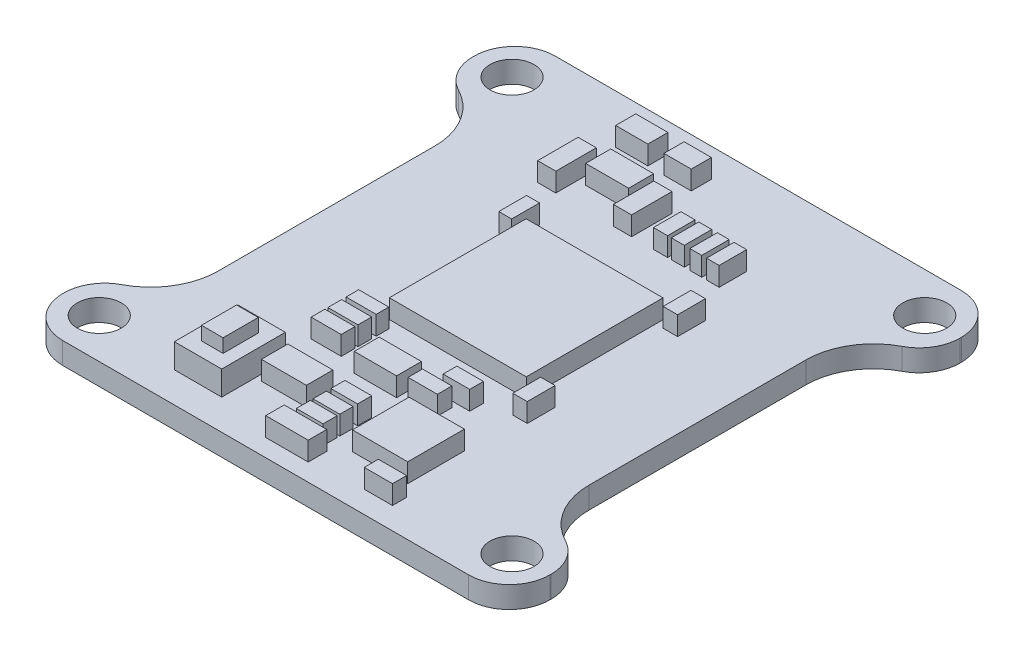
SolidWorks part; units mm, degrees
ref_plane "Front Plane" through (0, 0, 0) normal (0, 0, 1) x (1, 0, 0)
ref_plane "Top Plane" through (0, 0, 0) normal (0, 1, 0) x (1, 0, 0)
ref_plane "Right Plane" through (0, 0, 0) normal (1, 0, 0) x (0, 0, -1)
sketch "Sketch1" plane through (0, 0, 0) normal (0, 1, 0) x (1, 0, 0)
  line L0 (0, 18.2) -> (0, -18.2) construction
  line L1 (-18, 18.2) -> (18, 18.2)
  line L2 (-18, 18.2) -> (-18, -18.2)
  line L3 (-18, -18.2) -> (18, -18.2)
  line L4 (18, 18.2) -> (18, -18.2)
  line L5 (-18, 18.2) -> (18, -18.2) construction
  line L6 (-18, -18.2) -> (18, 18.2) construction
  line L7 (13.7, 18.2) -> (-13.7, 18.2)
  line L8 (13.7, 18.2) -> (13.7, -18.2)
  line L9 (13.7, -18.2) -> (-13.7, -18.2)
  line L10 (-13.7, 18.2) -> (-13.7, -18.2)
  line L11 (13.7, 18.2) -> (-13.7, -18.2) construction
  line L12 (13.7, -18.2) -> (-13.7, 18.2) construction
  line L13 (-18, 0) -> (18, 0) construction
  line L15 (18, 12.1) -> (-18, 12.1)
  line L16 (18, 12.1) -> (18, -12.1)
  line L17 (18, -12.1) -> (-18, -12.1)
  line L18 (-18, 12.1) -> (-18, -12.1)
  line L19 (18, 12.1) -> (-18, -12.1) construction
  line L20 (18, -12.1) -> (-18, 12.1) construction
  circle A0 centre (-15.25, 15.25) radius 1.625
  circle A1 centre (15.25, 15.25) radius 1.625
  circle A2 centre (15.25, -15.25) radius 1.625
  circle A3 centre (-15.25, -15.25) radius 1.625
  point P0 (0, 0)
  point P5 (0, 0)
  point P23 (0, 0)
  dimension "D4" = 3.25
  dimension "D1" = 36.4
  dimension "D2" = 36
  dimension "D3" = 27.4
  dimension "D5" = 30.5
  dimension "D6" = 30.5
  dimension "D7" = 24.2
extrude "PCB" add sketch "Sketch1" along normal blind 1.6 contours L15 L8 L1 L10 | L17 L8 L15 L10 | L4 L17 L8 L3 A2 | L8 L17 L10 L3 | L10 L17 L2 L3 A3 | L15 L4 L1 L8 A1 | L15 L10 L1 L2 A0 region at (-15.85, 0, -18.1254) region at (0, 0, -15.1499) region at (15.85, 0, -18.1254) region at (-15.85, 0, 12.1746) region at (0, 0, 0) region at (0, 0, 15.1499) region at (15.85, 0, 12.1746)
sketch "Sketch2" plane through (0, 1.6, 0) normal (0, 1, 0) x (1, 0, 0)
  line L1 (-4.269, -4.796) -> (5.8505, -4.796)
  line L2 (-4.269, -4.796) -> (-4.269, 5.3098)
  line L3 (-4.269, 5.3098) -> (5.8505, 5.3098)
  line L4 (5.8505, -4.796) -> (5.8505, 5.3098)
  line L5 (2.8219, -10.4297) -> (6.9091, -10.4297)
  line L6 (2.8219, -10.4297) -> (2.8219, -14.6149)
  line L7 (2.8219, -14.6149) -> (6.9091, -14.6149)
  line L8 (6.9091, -10.4297) -> (6.9091, -14.6149)
  line L9 (-5.6099, 11.0546) -> (-2.4369, 11.0546)
  line L10 (-5.6099, 11.0546) -> (-5.6099, 12.9056)
  line L11 (-5.6099, 12.9056) -> (-2.4369, 12.9056)
  line L12 (-2.4369, 11.0546) -> (-2.4369, 12.9056)
  line L13 (-6.9321, 14.5912) -> (-4.5523, 14.5912)
  line L14 (-6.9321, 14.5912) -> (-6.9321, 16.0786)
  line L15 (-6.9321, 16.0786) -> (-4.5523, 16.0786)
  line L16 (-4.5523, 14.5912) -> (-4.5523, 16.0786)
  line L17 (-3.3624, 14.5912) -> (-1.3461, 14.5912)
  line L18 (-3.3624, 14.5912) -> (-3.3624, 16.0786)
  line L19 (-3.3624, 16.0786) -> (-1.3461, 16.0786)
  line L20 (-1.3461, 14.5912) -> (-1.3461, 16.0786)
  line L21 (-1.7319, -11.5049) -> (-5.0578, -11.5049)
  line L22 (-1.7319, -11.5049) -> (-1.7319, -13.4629)
  line L23 (-1.7319, -13.4629) -> (-5.0578, -13.4629)
  line L24 (-5.0578, -11.5049) -> (-5.0578, -13.4629)
  line L25 (-7.5621, 9.4567) -> (-6.2179, 9.4567)
  line L26 (-7.5621, 9.4567) -> (-7.5621, 12.447)
  line L27 (-7.5621, 12.447) -> (-6.2179, 12.447)
  line L28 (-6.2179, 9.4567) -> (-6.2179, 12.447)
  line L29 (-1.9656, 9.4567) -> (-0.6214, 9.4567)
  line L30 (-1.9656, 9.4567) -> (-1.9656, 12.447)
  line L31 (-1.9656, 12.447) -> (-0.6214, 12.447)
  line L32 (-0.6214, 9.4567) -> (-0.6214, 12.447)
  line L33 (0.9972, 9.4567) -> (2.0397, 9.4567)
  line L34 (0.9972, 9.4567) -> (0.9972, 11.4868)
  line L35 (0.9972, 11.4868) -> (2.0397, 11.4868)
  line L36 (2.0397, 9.4567) -> (2.0397, 11.4868)
  line L37 (2.314, 9.4567) -> (3.2742, 9.4567)
  line L38 (2.314, 9.4567) -> (2.314, 11.4868)
  line L39 (2.314, 11.4868) -> (3.2742, 11.4868)
  line L40 (3.2742, 9.4567) -> (3.2742, 11.4868)
  line L41 (3.6857, 9.4567) -> (4.5636, 9.4567)
  line L42 (3.6857, 9.4567) -> (3.6857, 11.4868)
  line L43 (3.6857, 11.4868) -> (4.5636, 11.4868)
  line L44 (4.5636, 9.4567) -> (4.5636, 11.4868)
  line L45 (4.9202, 9.4567) -> (5.8505, 9.4567)
  line L46 (4.9202, 9.4567) -> (4.9202, 11.4868)
  line L47 (4.9202, 11.4868) -> (5.8505, 11.4868)
  line L48 (5.8505, 9.4567) -> (5.8505, 11.4868)
  line L49 (6.4017, 4.7655) -> (7.4716, 4.7655)
  line L50 (6.4017, 4.7655) -> (6.4017, 6.823)
  line L51 (6.4017, 6.823) -> (7.4716, 6.823)
  line L52 (7.4716, 4.7655) -> (7.4716, 6.823)
  line L53 (-5.7422, 4.7655) -> (-4.7913, 4.7655)
  line L54 (-5.7422, 4.7655) -> (-5.7422, 6.823)
  line L55 (-5.7422, 6.823) -> (-4.7913, 6.823)
  line L56 (-4.7913, 4.7655) -> (-4.7913, 6.823)
  line L57 (-5.9161, -8.9239) -> (-3.694, -8.9239)
  line L58 (-5.9161, -8.9239) -> (-5.9161, -7.9089)
  line L59 (-5.9161, -7.9089) -> (-3.694, -7.9089)
  line L60 (-3.694, -8.9239) -> (-3.694, -7.9089)
  line L61 (-5.9161, -7.6894) -> (-3.694, -7.6894)
  line L62 (-5.9161, -7.6894) -> (-5.9161, -6.6744)
  line L63 (-5.9161, -6.6744) -> (-3.694, -6.6744)
  line L64 (-3.694, -7.6894) -> (-3.694, -6.6744)
  line L65 (-5.9161, -6.3452) -> (-3.694, -6.3452)
  line L66 (-5.9161, -6.3452) -> (-5.9161, -5.4124)
  line L67 (-5.9161, -5.4124) -> (-3.694, -5.4124)
  line L68 (-3.694, -6.3452) -> (-3.694, -5.4124)
  line L69 (-2.1302, -9.5275) -> (0.9972, -9.5275)
  line L70 (-2.1302, -9.5275) -> (-2.1302, -7.6894)
  line L71 (-2.1302, -7.6894) -> (0.9972, -7.6894)
  line L72 (0.9972, -9.5275) -> (0.9972, -7.6894)
  line L73 (1.5185, -9.1983) -> (3.6857, -9.1983)
  line L74 (1.5185, -9.1983) -> (1.5185, -8.1283)
  line L75 (1.5185, -8.1283) -> (3.6857, -8.1283)
  line L76 (3.6857, -9.1983) -> (3.6857, -8.1283)
  line L77 (2.6021, -7.6894) -> (4.5636, -7.6894)
  line L78 (2.6021, -7.6894) -> (2.6021, -6.6744)
  line L79 (2.6021, -6.6744) -> (4.5636, -6.6744)
  line L80 (4.5636, -7.6894) -> (4.5636, -6.6744)
  line L81 (6.4017, -6.3452) -> (7.4716, -6.3452)
  line L82 (6.4017, -6.3452) -> (6.4017, -4.2876)
  line L83 (6.4017, -4.2876) -> (7.4716, -4.2876)
  line L84 (7.4716, -6.3452) -> (7.4716, -4.2876)
  line L85 (5.661, -16.5779) -> (7.7459, -16.5779)
  line L86 (5.661, -16.5779) -> (5.661, -15.5355)
  line L87 (5.661, -15.5355) -> (7.7459, -15.5355)
  line L88 (7.7459, -16.5779) -> (7.7459, -15.5355)
  line L89 (-1.2935, -16.9071) -> (1.8477, -16.9071)
  line L90 (-1.2935, -16.9071) -> (-1.2935, -15.5355)
  line L91 (-1.2935, -15.5355) -> (1.8477, -15.5355)
  line L92 (1.8477, -16.9071) -> (1.8477, -15.5355)
  line L93 (-0.6214, -15.316) -> (1.3539, -15.316)
  line L94 (-0.6214, -15.316) -> (-0.6214, -14.2735)
  line L95 (-0.6214, -14.2735) -> (1.3539, -14.2735)
  line L96 (1.3539, -15.316) -> (1.3539, -14.2735)
  line L97 (-0.6214, -14.0815) -> (1.3539, -14.0815)
  line L98 (-0.6214, -14.0815) -> (-0.6214, -13.0939)
  line L99 (-0.6214, -13.0939) -> (1.3539, -13.0939)
  line L100 (1.3539, -14.0815) -> (1.3539, -13.0939)
  line L101 (-0.6214, -12.7647) -> (1.3539, -12.7647)
  line L102 (-0.6214, -12.7647) -> (-0.6214, -11.7222)
  line L103 (-0.6214, -11.7222) -> (1.3539, -11.7222)
  line L104 (1.3539, -12.7647) -> (1.3539, -11.7222)
extrude "Top components" add sketch "Sketch2" along normal blind 1.4
fillet "Fillet1" radius 3 8 edges at (-18, 0.8, 12.1) (-18, 0.8, -12.1) (18, 0.8, -12.1) (18, 0.8, 12.1) (18, 0.8, 18.2) (-18, 0.8, 18.2) (-18, 0.8, -18.2) (18, 0.8, -18.2)
fillet "Fillet2" radius 5 4 edges at (13.7, 0.8, -12.1) (13.7, 0.8, 12.1) (-13.7, 0.8, 12.1) (-13.7, 0.8, -12.1)
sketch "Sketch3" plane through (0, 0, 0) normal (0, -1, 0) x (1, 0, 0)
  line L1 (10.2944, -10.6941) -> (6.7006, -10.6941)
  line L2 (10.2944, -10.6941) -> (10.2944, -14.7917)
  line L3 (10.2944, -14.7917) -> (6.7006, -14.7917)
  line L4 (6.7006, -10.6941) -> (6.7006, -14.7917)
  line L5 (10.2944, -15.1612) -> (6.7006, -15.1612)
  line L6 (10.2944, -15.1612) -> (10.2944, -17.042)
  line L7 (10.2944, -17.042) -> (6.7006, -17.042)
  line L8 (6.7006, -15.1612) -> (6.7006, -17.042)
  line L9 (4.2563, -13.2248) -> (1.2177, -13.2248)
  line L10 (4.2563, -13.2248) -> (4.2563, -15.1612)
  line L11 (4.2563, -15.1612) -> (1.2177, -15.1612)
  line L12 (1.2177, -13.2248) -> (1.2177, -15.1612)
  line L13 (4.5072, -10.1304) -> (1.0226, -10.1304)
  line L14 (4.5072, -10.1304) -> (4.5072, -12.054)
  line L15 (4.5072, -12.054) -> (1.0226, -12.054)
  line L16 (1.0226, -10.1304) -> (1.0226, -12.054)
  line L17 (1.0226, -12.2491) -> (-0.1762, -12.2491)
  line L18 (1.0226, -12.2491) -> (1.0226, -14.3678)
  line L19 (1.0226, -14.3678) -> (-0.1762, -14.3678)
  line L20 (-0.1762, -12.2491) -> (-0.1762, -14.3678)
  line L21 (1.0226, -14.5629) -> (-0.1762, -14.5629)
  line L22 (1.0226, -14.5629) -> (1.0226, -16.6816)
  line L23 (1.0226, -16.6816) -> (-0.1762, -16.6816)
  line L24 (-0.1762, -14.5629) -> (-0.1762, -16.6816)
  line L25 (-0.1762, -8.3463) -> (-2.3506, -8.3463)
  line L26 (-0.1762, -8.3463) -> (-0.1762, -9.5729)
  line L27 (-0.1762, -9.5729) -> (-2.3506, -9.5729)
  line L28 (-2.3506, -8.3463) -> (-2.3506, -9.5729)
  line L29 (-0.1762, -9.8517) -> (-2.3506, -9.8517)
  line L30 (-0.1762, -9.8517) -> (-0.1762, -10.6941)
  line L31 (-0.1762, -10.6941) -> (-2.3506, -10.6941)
  line L32 (-2.3506, -9.8517) -> (-2.3506, -10.6941)
  line L33 (-5.5286, -0.1783) -> (-7.1733, -0.1783)
  line L34 (-5.5286, -0.1783) -> (-5.5286, -3.5793)
  line L35 (-5.5286, -3.5793) -> (-7.1733, -3.5793)
  line L36 (-7.1733, -0.1783) -> (-7.1733, -3.5793)
  line L37 (-4.8038, -8.9038) -> (-8.6229, -8.9038)
  line L38 (-4.8038, -8.9038) -> (-4.8038, -10.6941)
  line L39 (-4.8038, -10.6941) -> (-8.6229, -10.6941)
  line L40 (-8.6229, -8.9038) -> (-8.6229, -10.6941)
  line L41 (7.9082, 9.4672) -> (6.821, 9.4672)
  line L42 (7.9082, 9.4672) -> (7.9082, 7.3206)
  line L43 (7.9082, 7.3206) -> (6.821, 7.3206)
  line L44 (6.821, 9.4672) -> (6.821, 7.3206)
  line L45 (6.5767, -1.1077) -> (4.5069, -1.1077)
  line L46 (6.5767, -1.1077) -> (6.5767, -2.197)
  line L47 (6.5767, -2.197) -> (4.5069, -2.197)
  line L48 (4.5069, -1.1077) -> (4.5069, -2.197)
  line L49 (6.5549, -2.3277) -> (4.5287, -2.3277)
  line L50 (6.5549, -2.3277) -> (6.5549, -3.2537)
  line L51 (6.5549, -3.2537) -> (4.5287, -3.2537)
  line L52 (4.5287, -2.3277) -> (4.5287, -3.2537)
  line L53 (6.5984, -3.5151) -> (4.4852, -3.5151)
  line L54 (6.5984, -3.5151) -> (6.5984, -4.5064)
  line L55 (6.5984, -4.5064) -> (4.4852, -4.5064)
  line L56 (4.4852, -3.5151) -> (4.4852, -4.5064)
  line L57 (4.3327, -1.1948) -> (2.9819, -1.1948)
  line L58 (4.3327, -1.1948) -> (4.3327, -4.2341)
  line L59 (4.3327, -4.2341) -> (2.9819, -4.2341)
  line L60 (2.9819, -1.1948) -> (2.9819, -4.2341)
  line L61 (1.9144, -2.0009) -> (-0.09, -2.0009)
  line L62 (1.9144, -2.0009) -> (1.9144, -3.0685)
  line L63 (1.9144, -3.0685) -> (-0.09, -3.0685)
  line L64 (-0.09, -2.0009) -> (-0.09, -3.0685)
  line L65 (-0.3042, -1.9155) -> (-3.3247, -1.9155)
  line L66 (-0.3042, -1.9155) -> (-0.3042, -3.3477)
  line L67 (-0.3042, -3.3477) -> (-3.3247, -3.3477)
  line L68 (-3.3247, -1.9155) -> (-3.3247, -3.3477)
  line L69 (1.3884, 2.1336) -> (0.3208, 2.1336)
  line L70 (1.3884, 2.1336) -> (1.3884, 0.1025)
  line L71 (1.3884, 0.1025) -> (0.3208, 0.1025)
  line L72 (0.3208, 2.1336) -> (0.3208, 0.1025)
  line L73 (0.2296, 2.1076) -> (-0.6818, 2.1076)
  line L74 (0.2296, 2.1076) -> (0.2296, 0.1025)
  line L75 (0.2296, 0.1025) -> (-0.6818, 0.1025)
  line L76 (-0.6818, 2.1076) -> (-0.6818, 0.1025)
  line L77 (1.3493, -0.1709) -> (-0.6297, -0.1709)
  line L78 (1.3493, -0.1709) -> (1.3493, -1.2255)
  line L79 (1.3493, -1.2255) -> (-0.6297, -1.2255)
  line L80 (-0.6297, -0.1709) -> (-0.6297, -1.2255)
  line L81 (-1.1114, 1.1311) -> (-4.171, 1.1311)
  line L82 (-1.1114, 1.1311) -> (-1.1114, -0.7958)
  line L83 (-1.1114, -0.7958) -> (-4.171, -0.7958)
  line L84 (-4.171, 1.1311) -> (-4.171, -0.7958)
  line L85 (-4.085, -4.0984) -> (-6.0958, -4.0984)
  line L86 (-4.085, -4.0984) -> (-4.085, -5.1394)
  line L87 (-4.085, -5.1394) -> (-6.0958, -5.1394)
  line L88 (-6.0958, -4.0984) -> (-6.0958, -5.1394)
  line L89 (-4.0672, -5.2818) -> (-6.1136, -5.2818)
  line L90 (-4.0672, -5.2818) -> (-4.0672, -6.3406)
  line L91 (-4.0672, -6.3406) -> (-6.1136, -6.3406)
  line L92 (-6.1136, -5.2818) -> (-6.1136, -6.3406)
  line L93 (6.5446, -16.067) -> (4.3875, -16.067)
  line L94 (6.5446, -16.067) -> (6.5446, -17.1304)
  line L95 (6.5446, -17.1304) -> (4.3875, -17.1304)
  line L96 (4.3875, -16.067) -> (4.3875, -17.1304)
  line L97 (5.9674, -13.287) -> (4.8736, -13.287)
  line L98 (5.9674, -13.287) -> (5.9674, -15.3379)
  line L99 (5.9674, -15.3379) -> (4.8736, -15.3379)
  line L100 (4.8736, -13.287) -> (4.8736, -15.3379)
  line L101 (6.2104, -10.0513) -> (4.7825, -10.0513)
  line L102 (6.2104, -10.0513) -> (6.2104, -12.4819)
  line L103 (6.2104, -12.4819) -> (4.7825, -12.4819)
  line L104 (4.7825, -10.0513) -> (4.7825, -12.4819)
extrude "Rear components" add sketch "Sketch3" along normal blind 1.4
sketch "Sketch4" plane through (0, 1.6, 0) normal (0, 1, 0) x (1, 0, 0)
  line L0 (-15, -18.2) -> (15, -18.2) construction
  line L1 (-9, -11.25) -> (-5.5, -11.25)
  line L2 (-9, -11.25) -> (-9, -15.95)
  line L3 (-9, -15.95) -> (-5.5, -15.95)
  line L4 (-5.5, -11.25) -> (-5.5, -15.95)
  dimension "D1" = 3.5
  dimension "D2" = 4.7
  dimension "D3" = 9
  dimension "D4" = 2.25
extrude "Button base" add sketch "Sketch4" along normal blind 1.8
sketch "Sketch5" plane through (0, 3.4, 0) normal (0, 1, 0) x (1, 0, 0)
  line L0 (-9, -11.25) -> (-5.5, -15.95) construction
  line L2 (-8.05, -12.3) -> (-6.45, -12.3)
  line L3 (-8.05, -12.3) -> (-8.05, -14.9)
  line L4 (-8.05, -14.9) -> (-6.45, -14.9)
  line L5 (-6.45, -12.3) -> (-6.45, -14.9)
  line L6 (-8.05, -12.3) -> (-6.45, -14.9) construction
  line L7 (-8.05, -14.9) -> (-6.45, -12.3) construction
  point P4 (-7.25, -13.6)
  dimension "D1" = 1.6
  dimension "D2" = 2.6
extrude "Button tip" add sketch "Sketch5" along normal blind 1
